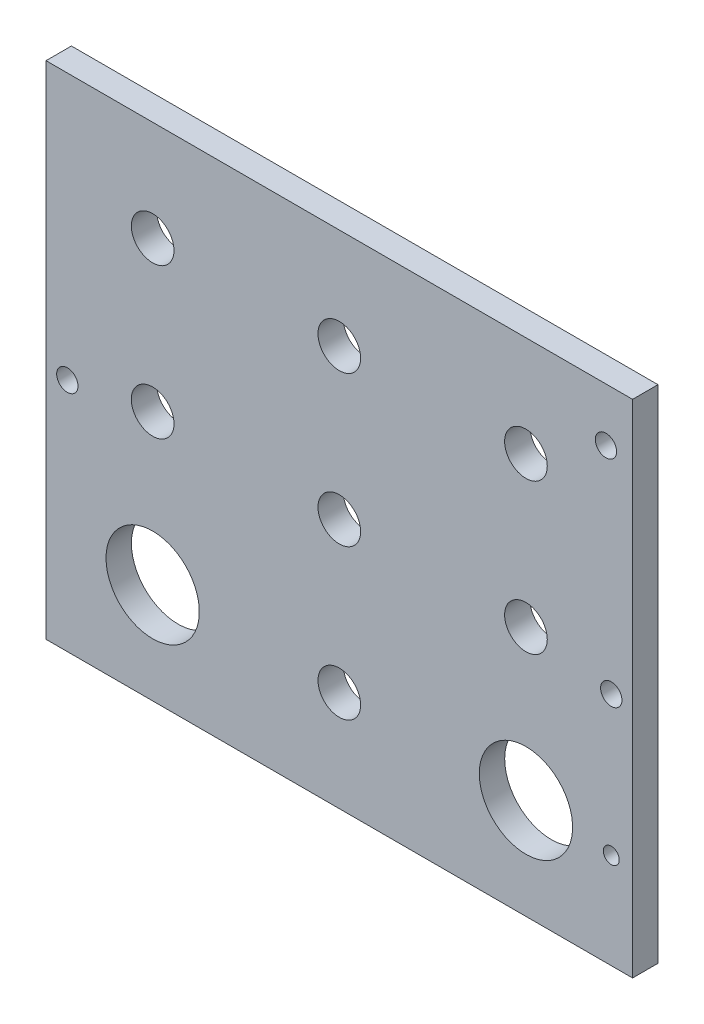
SolidWorks part; units mm, degrees
ref_plane "Alzado" through (0, 0, 0) normal (0, 0, 1) x (1, 0, 0)
ref_plane "Planta" through (0, 0, 0) normal (0, 1, 0) x (1, 0, 0)
ref_plane "Vista lateral" through (0, 0, 0) normal (1, 0, 0) x (0, 0, -1)
sketch "Croquis1" plane through (0, 0, 0) normal (0, 0, 1) x (1, 0, 0)
  line L1 (0, 0) -> (90, 0)
  line L2 (0, 0) -> (0, 76.2)
  line L3 (0, 76.2) -> (90, 76.2)
  line L4 (90, 0) -> (90, 76.2)
  circle A0 centre (45, 38.1) radius 4
  circle A1 centre (10, 9.95) radius 4
  circle A2 centre (10, 66.25) radius 4
  circle A3 centre (80, 66.25) radius 4
  circle A4 centre (80, 9.95) radius 4
  circle A5 centre (45, 66.25) radius 4
  circle A6 centre (10, 38.1) radius 4
  circle A7 centre (80, 38.1) radius 4
  circle A8 centre (45, 9.95) radius 4
  dimension "D3" = 8
  dimension "D5" = 8
  dimension "D7" = 8
  dimension "D10" = 8
  dimension "D11" = 8
  dimension "D12" = 8
  dimension "D13" = 8
  dimension "D14" = 8
  dimension "D15" = 8
  dimension "D1" = 76.2
  dimension "D2" = 90
  dimension "D4" = 10
  dimension "D6" = 9.95
  dimension "D8" = 9.95
  dimension "D9" = 10
extrude "Saliente-Extruir1" add sketch "Croquis1" along normal blind 0.4763
sketch "Croquis2" plane through (0, 0, 0.4763) normal (0, 0, 1) x (1, 0, 0)
extrude "Saliente-Extruir2" add sketch "Croquis1<2>" along normal blind 4.7625
sketch "Croquis1<2>" plane through (0, 0, 0) normal (0, 0, 1) x (1, 0, 0) same geometry as "Croquis1"
sketch "Croquis3" plane through (0, 0, 0) normal (0, -1, 0) x (1, 0, 0)
  line L1 (90, 4.7625) -> (0, 4.7625)
  line L2 (90, 4.7625) -> (90, 0)
  line L3 (90, 0) -> (0, 0)
  line L4 (0, 4.7625) -> (0, 0)
extrude "Saliente-Extruir3" add sketch "Croquis3" along normal blind 4.445
sketch "Croquis5" plane through (0, 76.2, 0) normal (0, 1, 0) x (1, 0, 0)
  line L1 (90, -4.7625) -> (0, -4.7625)
  line L2 (90, -4.7625) -> (90, 0)
  line L3 (90, 0) -> (0, 0)
  line L4 (0, -4.7625) -> (0, 0)
extrude "Saliente-Extruir4" add sketch "Croquis5" along normal blind 4.445
sketch "Croquis6" plane through (0, 0, 0) normal (-1, 0, 0) x (0, 0, 1)
  line L1 (0, -4.445) -> (4.7625, -4.445)
  line L2 (0, -4.445) -> (0, 80.645)
  line L3 (0, 80.645) -> (4.7625, 80.645)
  line L4 (4.7625, -4.445) -> (4.7625, 80.645)
extrude "Saliente-Extruir5" add sketch "Croquis6" along normal blind 5
sketch "Croquis7" plane through (90, 0, 0) normal (1, 0, 0) x (0, 0, -1)
  line L1 (0, -4.445) -> (-4.7625, -4.445)
  line L2 (0, -4.445) -> (0, 80.645)
  line L3 (0, 80.645) -> (-4.7625, 80.645)
  line L4 (-4.7625, -4.445) -> (-4.7625, 80.645)
extrude "Saliente-Extruir6" add sketch "Croquis7" along normal blind 5
sketch "Croquis8" plane through (0, -4.445, 0) normal (0, -1, 0) x (1, 0, 0)
  line L1 (95, 0) -> (-5, 0)
  line L2 (95, 0) -> (95, 4.7625)
  line L3 (95, 4.7625) -> (-5, 4.7625)
  line L4 (-5, 0) -> (-5, 4.7625)
extrude "Saliente-Extruir7" add sketch "Croquis8" along normal blind 4.445
sketch "Croquis9" plane through (0, 80.645, 0) normal (0, 1, 0) x (1, 0, 0)
  line L1 (95, 0) -> (-5, 0)
  line L2 (95, 0) -> (95, -4.7625)
  line L3 (95, -4.7625) -> (-5, -4.7625)
  line L4 (-5, 0) -> (-5, -4.7625)
extrude "Saliente-Extruir8" add sketch "Croquis9" along normal blind 4.445
sketch "Croquis10" plane through (95, 0, 0) normal (1, 0, 0) x (0, 0, -1)
  line L1 (0, -8.89) -> (-4.7625, -8.89)
  line L2 (0, -8.89) -> (0, 85.09)
  line L3 (0, 85.09) -> (-4.7625, 85.09)
  line L4 (-4.7625, -8.89) -> (-4.7625, 85.09)
extrude "Saliente-Extruir9" add sketch "Croquis10" along normal blind 5
sketch "Croquis12" plane through (-5, 0, 0) normal (-1, 0, 0) x (0, 0, 1)
  line L1 (0, -8.89) -> (4.7625, -8.89)
  line L2 (0, -8.89) -> (0, 85.09)
  line L3 (0, 85.09) -> (4.7625, 85.09)
  line L4 (4.7625, -8.89) -> (4.7625, 85.09)
extrude "Saliente-Extruir10" add sketch "Croquis12" along normal blind 5
sketch "Sketch1" plane through (0, 0, 0) normal (0, 0, -1) x (-1, 0, 0)
  circle A0 centre (-80, 9.95) radius 8.75
  circle A1 centre (-10, 9.95) radius 8.75
  dimension "D1" = 17.5
  dimension "D2" = 17.5
extrude "Cut-Extrude1" cut sketch "Sketch1" against normal blind 10
sketch "Sketch2" plane through (0, 0, 0) normal (0, 0, -1) x (-1, 0, 0)
  circle A0 centre (-95, 75.09) radius 2
extrude "Cut-Extrude2" cut sketch "Sketch2" against normal blind 10
sketch "Sketch3" plane through (0, 0, 4.7625) normal (0, 0, 1) x (1, 0, 0)
  circle A0 centre (96, 9.0265) radius 1.5
extrude "Cut-Extrude3" cut sketch "Sketch3" against normal blind 10
sketch "Sketch4" plane through (0, 0, 0) normal (0, 0, -1) x (-1, 0, 0)
  line L0 (10, 85.09) -> (10, -8.89) construction
  line L1 (-100, -8.89) -> (-100, 85.09) construction
  circle A0 centre (6, 35.2204) radius 2
  circle A1 centre (-96, 35.2204) radius 2
  dimension "D1" = 4
  dimension "D2" = 4
  dimension "D3" = 4
extrude "Cut-Extrude4" cut sketch "Sketch4" against normal blind 10
